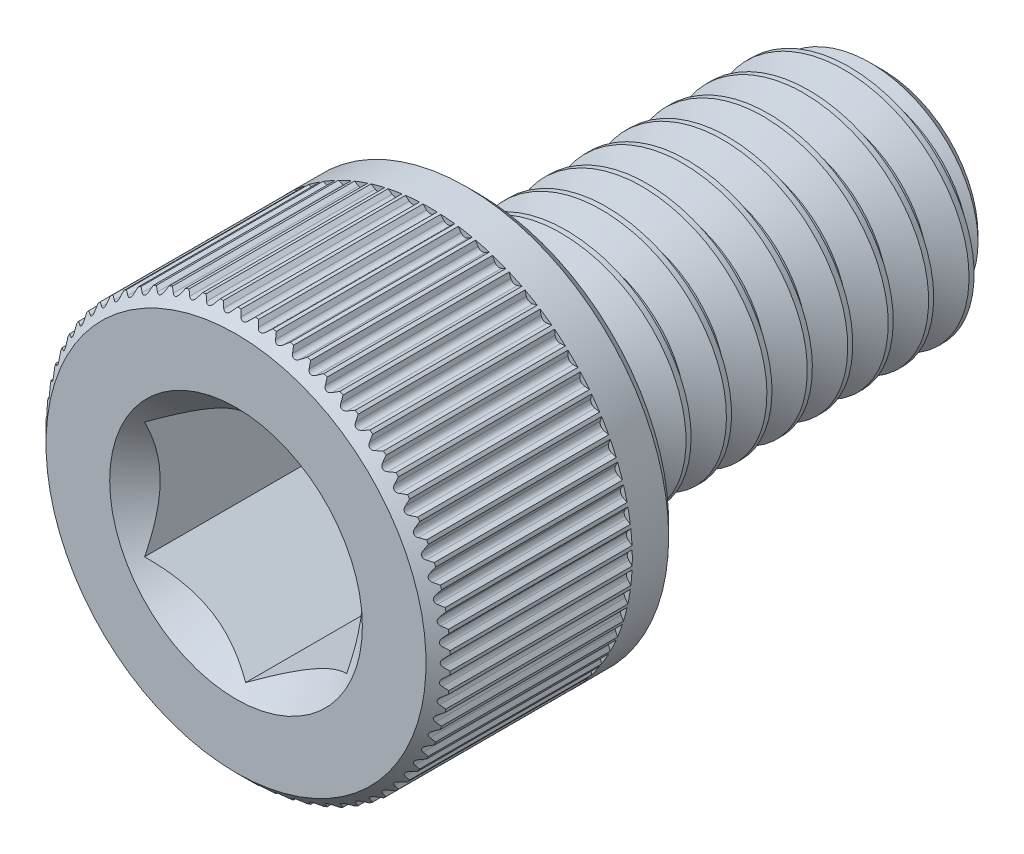
SolidWorks part; units mm, degrees
ref_plane "Front Plane" through (0, 0, 0) normal (0, 0, 1) x (1, 0, 0)
ref_plane "Top Plane" through (0, 0, 0) normal (0, 1, 0) x (1, 0, 0)
ref_plane "Right Plane" through (0, 0, 0) normal (1, 0, 0) x (0, 0, -1)
sketch "Sketch1" plane through (0, 0, 0) normal (1, 0, 0) x (0, 0, -1)
  line L0 (-8, 0) -> (8, 0) construction
  line L1 (8, 0) -> (8, 2.3505) construction
  line L2 (8, 2.3505) -> (7.3505, 3) construction
  line L3 (7.3505, 3) -> (7.25, 3) construction
  line L4 (7.25, 3) -> (-2, 3) construction
  line L5 (-2, 3) -> (-2, 5) construction
  line L6 (-2, 5) -> (-8, 5) construction
  line L7 (-8, 5) -> (-8, 0) construction
  line L8 (8, 2.3505) -> (8, 3) construction
  line L9 (7.9375, 3.1083) -> (8.4375, 2.2422) construction
  line L10 (8.4375, 2.2422) -> (8.9375, 3.1083) construction
  line L11 (8.9375, 3.1083) -> (7.9375, 3.1083) construction
  line L12 (8.4375, 3.1083) -> (8.4375, 3) construction
  line L13 (8.4375, 2.2422) -> (8.4375, 2.3505) construction
  line L14 (8.375, 2.3505) -> (8.5, 2.3505) construction
  line L15 (8, 3) -> (8.875, 3) construction
  line L16 (7.9687, 3.0541) -> (8.9063, 3.0541) construction
  line L17 (8, 0) -> (8, -3) construction
  line L18 (-2.3, 5) -> (-2, 4.7) construction
  line L19 (-7.7, 5) -> (-8, 4.7) construction
  line L20 (-2, 3) -> (-2, 0) construction
  line L21 (-2, 1.5) -> (1.3333, 1.5) construction
  line L22 (1.3333, 1.5) -> (4.6667, 1.5) construction
  line L23 (4.6667, 1.5) -> (8, 1.5) construction
  line L24 (1.3333, 1.5) -> (1.3333, 3) construction
  line L25 (1.3333, 3) -> (1.3333, 5) construction
  line L26 (4.6667, 1.5) -> (4.6667, 5) construction
  point P0 (-8, 2.5)
  point P3 (5.5, 3)
  point P4 (0, 0)
  point P18 (4.6667, 3)
  point P22 (8.4375, 2.3505)
  point P24 (7.25, 3)
  point P25 (8.4375, 3)
  point P28 (8.4375, 3.0541)
  point P29 (5.5, -3)
  point P30 (1.3333, 3)
  point P31 (-5, 5)
  point P37 (-3.05, 5)
  point P38 (-7.55, 5)
  point P45 (1.3333, 1.5)
  point P46 (4.6667, 1.5)
  dimension "D2" = 0.125
  dimension "D7" = 0.3
  dimension "D8" = 0.3
  dimension "D9" = 0.3
  dimension "D10" = 0.15
  dimension "D11" = 0.75
  dimension "Drive Size" = 5
  dimension "Head Diameter" = 10
  dimension "Head Height" = 6
  dimension "Thread Pitch" = 1
  dimension "Thread Size" = 6
  dimension "Length" = 10
  dimension "D12" = 0.75
  dimension "D4" = 2.5
  dimension "D3" = 45
sketch "Sketch2" plane through (0, 0, 0) normal (1, 0, 0) x (0, 0, -1)
  line L0 (-8, 0) -> (-8, 4.7)
  line L1 (-7.7, 5) -> (-2.3, 5)
  line L2 (-2, 4.7) -> (-2, 3.3)
  line L4 (7.3505, 3) -> (8, 2.3505)
  line L5 (8, 2.3505) -> (8, 0)
  line L6 (-2, 5) -> (-8, 5) construction
  line L7 (8, 0) -> (-8, 0)
  line L8 (-7.7, 5) -> (-8, 4.7) construction
  line L10 (-7.7, 5) -> (-8, 4.7)
  line L14 (-2.3, 5) -> (-2, 4.7) construction
  line L16 (-2.3, 5) -> (-2, 4.7)
  line L17 (-2, 3) -> (-2, 5) construction
  line L19 (-1.7, 3) -> (7.3505, 3)
  line L20 (7.25, 3) -> (-2, 3) construction
  arc A1 (-2, 3.3) -> (-1.7, 3) centre (-1.7, 3.3) ccw
  dimension "D3" = 0.3
revolve "Revolve1" add sketch "Sketch2" angle 360 about L7
sketch "Sketch3" plane through (0, 0, 8) normal (0, 0, 1) x (1, 0, 0)
  line L1 (2.5, -1.4434) -> (2.5, 1.4434)
  line L2 (2.5, 1.4434) -> (0, 2.8868)
  line L3 (0, 2.8868) -> (-2.5, 1.4434)
  line L4 (-2.5, 1.4434) -> (-2.5, -1.4434)
  line L5 (-2.5, -1.4434) -> (0, -2.8868)
  line L6 (0, -2.8868) -> (2.5, -1.4434)
  circle A0 centre (0, 0) radius 2.5 construction
  circle A1 centre (0, 0) radius 5 construction
  circle A2 centre (0, 0) radius 5 construction
  circle A3 centre (0, 0) radius 2.8868 construction
  point P13 (0, 0)
extrude "Cut-Extrude1" cut sketch "Sketch3" against normal offset from surface (5 mm away) 1 up to face at (0, 4.7, 2)
sketch "Sketch4" plane through (0, 0, 8) normal (0, 0, 1) x (1, 0, 0)
  circle A0 centre (0, 0) radius 3.125
  dimension "D1" = 6.25
extrude "Cut-Extrude2" cut sketch "Sketch4" against normal up to vertex (3 mm away) draft 45 up to point (0, 5, 5)
sketch "Sketch11" plane through (0, 0, 0) normal (1, 0, 0) x (0, 0, -1)
  line L0 (-8, 0) -> (8, 0) construction
  line L1 (-8, 0) -> (8, 0) construction
  line L2 (-0.125, 0) -> (-0.125, 3) construction
  line L3 (7.25, 3) -> (-2, 3) construction
  line L4 (6.125, 0) -> (6.125, 3) construction
  line L6 (8, 2.3505) -> (8, 3) construction
  point P2 (-0.125, 0)
  point P3 (6.125, 0)
  dimension "D1" = 1.875
  dimension "D2" = 1.875
sketch "Sketch6" plane through (0, 0, -8) normal (0, 0, -1) x (-1, 0, 0)
  circle A0 centre (0, 0) radius 3
curve "Helix/Spiral1" pitch 1 height 11 turns 11
sketch "Sketch10" plane through (0, 0, 0) normal (1, 0, 0) x (0, 0, -1)
  line L0 (-1.7, -5) -> (-1.7, 5)
  line L5 (-8, 0) -> (8, 0) construction
  line L6 (-1.7, 3) -> (-1.7, -3) construction
  point P3 (-1.7, 0)
split "Split1" trim tools "Sketch10" bodies to split 106 resulting bodies 114 115
sketch "Sketch7" plane through (0, 0, 0) normal (1, 0, 0) x (0, 0, -1)
  line L0 (7.9687, 3.0541) -> (8.9063, 3.0541)
  line L1 (8.9063, 3.0541) -> (8.5, 2.3505)
  line L2 (8.5, 2.3505) -> (8.375, 2.3505)
  line L3 (8.375, 2.3505) -> (7.9687, 3.0541)
sweep "Cut-Sweep1" cut profiles "Sketch7" path "Helix/Spiral1" align with end faces yes
sketch "Sketch8" plane through (0, 0, 0) normal (1, 0, 0) x (0, 0, -1)
  line L0 (-2, 0) -> (-2, 3)
  line L1 (-1.7, -3) -> (-1.7, 3) construction
  line L2 (-2, 3) -> (-1.7, 3)
  line L4 (-1.7, 3) -> (0.0321, 0)
  line L5 (0.0321, 0) -> (-2, 0)
  line L6 (7.25, 3) -> (-2, 3) construction
  line L7 (-8, 0) -> (8, 0) construction
  dimension "D1" = 60
revolve "Revolve2" add sketch "Sketch8" angle 360 about L5
ref_plane "Plane1" through (0, 0, 8) normal (0, 0, 1) x (1, 0, 0)
sketch "Sketch12" plane through (0, 0, 8) normal (0, 0, 1) x (1, 0, 0)
  line L0 (0, 0) -> (0.1745, 4.997) construction
  line L1 (0, 0) -> (-0.1745, 4.997) construction
  line L2 (0, 4.875) -> (0, 5.125) construction
  line L3 (-0.3025, 5.125) -> (0.3025, 5.125)
  line L4 (-0.3025, 5.125) -> (-0.0897, 4.9122)
  line L5 (0.0897, 4.9122) -> (0.3025, 5.125)
  circle A0 centre (0, 0) radius 5 construction
  arc A1 (-0.0897, 4.9122) -> (0.0897, 4.9122) centre (0, 5.0019) ccw
  point P9 (0, 5.125)
  point P13 (0, 5)
  dimension "D2" = 0.125
  dimension "D1" = 4
extrude "Cut-Extrude3" cut sketch "Sketch12" against normal blind 4.8
pattern_circular "CirPattern1" count 72 over 360 about axis through (0, 0, 0) along (0, 0, 1) of "Cut-Extrude3"
equation "\"D2@Sketch1\" = \"Thread Pitch@Sketch1\" / 8"
equation "\"D4@Helix/Spiral1\" = \"Thread Pitch@Sketch1\""
equation "\"D7@Sketch1\" = \"Head Height@Sketch1\" * .05"
equation "\"D8@Sketch1\"=\"D7@Sketch1\""
equation "\"D9@Sketch1\"=\"D7@Sketch1\""
equation "\"D10@Sketch1\"=\"D7@Sketch1\"/2"
equation "\"D11@Sketch1\"=\"D10@Sketch1\"*5"
equation "\"D4@Sketch1\"=\"Thread Pitch@Sketch1\"*2.5"
equation "\"D12@Sketch1\"=\"Thread Pitch@Sketch1\"*.75"
equation "\"D3@Helix/Spiral1\"=\"Length@Sketch1\"+\"Thread Pitch@Sketch1\""
equation "\"D3@Sketch2\" = \"Thread Size@Sketch1\" * 0.05"
equation "\"D1@Sketch11\"=\"Length@Sketch1\"*0.1875"
equation "\"D2@Sketch11\"=\"D1@Sketch11\""
equation "\"D2@Sketch12\"=\"Head Diameter@Sketch1\"*.0125"
equation "\"D1@Cut-Extrude3\"=\"Head Height@Sketch1\"*.8"
equation "\"D1@CirPattern1\"=\"D3@CirPattern1\"/(1.25*\"D1@Sketch12\")"
equation "\"D1@Sketch4\"=\"Drive Size@Sketch1\"*1.25"
